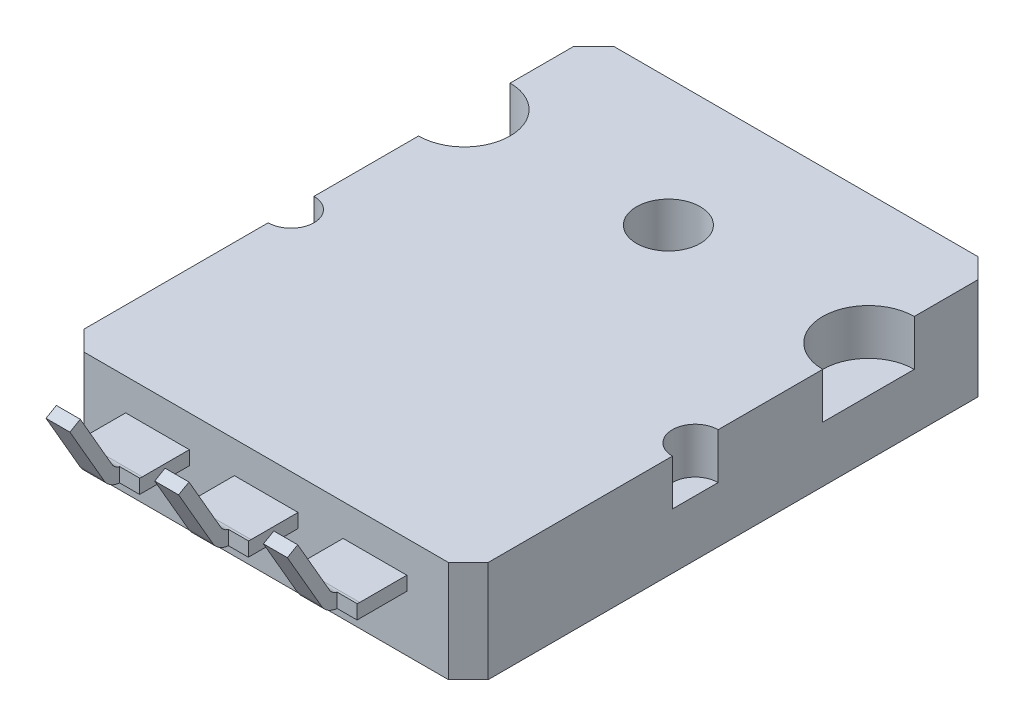
SolidWorks part; units mm, degrees
ref_plane "Спереди" through (0, 0, 0) normal (0, 0, 1) x (1, 0, 0)
ref_plane "Сверху" through (0, 0, 0) normal (0, 1, 0) x (1, 0, 0)
ref_plane "Справа" through (0, 0, 0) normal (1, 0, 0) x (0, 0, -1)
ref_plane "Плоскость1" through (0, 2.3, 0) normal (0, 1, 0) x (1, 0, 0)
sketch "Эскиз1" plane through (0, 2.3, 0) normal (0, 1, 0) x (1, 0, 0)
  line L0 (-10.15, -13.3) -> (10.15, -13.3)
  line L1 (10.15, -13.3) -> (10.15, 13.3)
  line L2 (10.15, 13.3) -> (-10.15, 13.3)
  line L3 (-10.15, 13.3) -> (-10.15, -13.3)
extrude "Бобышка-Вытянуть1" add sketch "Эскиз1" against normal blind 5.1
sketch "Эскиз2" plane through (0, 0, 13.3) normal (0, 0, 1) x (1, 0, 0)
  line L0 (3.861, 0) -> (3.861, 0.7)
  line L1 (3.861, 0.7) -> (7.061, 0.7)
  line L2 (7.061, 0.7) -> (7.061, 0)
  line L3 (7.061, 0) -> (3.861, 0)
extrude "Бобышка-Вытянуть2" add sketch "Эскиз2" along normal blind 3
sketch "Эскиз3" plane through (0, 0, 0) normal (0, -1, 0) x (1, 0, 0)
  line L0 (3.861, 15.8) -> (4.861, 15.8)
  line L1 (4.861, 15.8) -> (4.861, 18.3)
  line L2 (4.861, 18.3) -> (3.861, 18.3)
  line L3 (3.861, 18.3) -> (3.861, 15.8)
extrude "Вырез-Вытянуть1" cut sketch "Эскиз3" against normal through all
sketch "Эскиз4" plane through (0, 0, 0) normal (0, -1, 0) x (1, 0, 0)
  line L0 (6.061, 18.3) -> (6.061, 15.8)
  line L1 (6.061, 15.8) -> (7.061, 15.8)
  line L2 (7.061, 15.8) -> (7.061, 18.3)
  line L3 (7.061, 18.3) -> (6.061, 18.3)
extrude "Вырез-Вытянуть2" cut sketch "Эскиз4" against normal through all
sketch "Эскиз6" plane through (0, 0, 13.3) normal (0, 0, 1) x (1, 0, 0)
  line L0 (-1.6, 0) -> (-1.6, 0.7)
  line L1 (-1.6, 0.7) -> (1.6, 0.7)
  line L2 (1.6, 0.7) -> (1.6, 0)
  line L3 (1.6, 0) -> (-1.6, 0)
extrude "Бобышка-Вытянуть4" add sketch "Эскиз6" along normal blind 3
sketch "Эскиз7" plane through (0, 0, 0) normal (0, -1, 0) x (1, 0, 0)
  line L0 (-0.6, 15.8) -> (-0.6, 18.3)
  line L1 (-0.6, 18.3) -> (-1.6, 18.3)
  line L2 (-1.6, 18.3) -> (-1.6, 15.8)
  line L3 (-1.6, 15.8) -> (-0.6, 15.8)
extrude "Вырез-Вытянуть3" cut sketch "Эскиз7" against normal through all
sketch "Эскиз8" plane through (0, 0, 0) normal (0, -1, 0) x (1, 0, 0)
  line L0 (1.6, 18.3) -> (0.6, 18.3)
  line L1 (0.6, 18.3) -> (0.6, 15.8)
  line L2 (0.6, 15.8) -> (1.6, 15.8)
  line L3 (1.6, 15.8) -> (1.6, 18.3)
extrude "Вырез-Вытянуть4" cut sketch "Эскиз8" against normal through all
sketch "Эскиз10" plane through (0, 0, 13.3) normal (0, 0, 1) x (1, 0, 0)
  line L0 (-7.061, 0) -> (-7.061, 0.7)
  line L1 (-7.061, 0.7) -> (-3.861, 0.7)
  line L2 (-3.861, 0.7) -> (-3.861, 0)
  line L3 (-3.861, 0) -> (-7.061, 0)
extrude "Бобышка-Вытянуть6" add sketch "Эскиз10" along normal blind 3
sketch "Эскиз11" plane through (0, 0, 0) normal (0, -1, 0) x (1, 0, 0)
  line L0 (-6.061, 15.8) -> (-6.061, 18.3)
  line L1 (-6.061, 18.3) -> (-7.061, 18.3)
  line L2 (-7.061, 18.3) -> (-7.061, 15.8)
  line L3 (-7.061, 15.8) -> (-6.061, 15.8)
extrude "Вырез-Вытянуть5" cut sketch "Эскиз11" against normal through all
sketch "Эскиз12" plane through (0, 0, 0) normal (0, -1, 0) x (1, 0, 0)
  line L0 (-3.861, 18.3) -> (-4.861, 18.3)
  line L1 (-4.861, 18.3) -> (-4.861, 15.8)
  line L2 (-4.861, 15.8) -> (-3.861, 15.8)
  line L3 (-3.861, 15.8) -> (-3.861, 18.3)
extrude "Вырез-Вытянуть6" cut sketch "Эскиз12" against normal through all
hole_wizard "Диаметр отверстия Ø3.2 (3.2)1" positions "Эскиз15" profile "Эскиз14" hole size "Ø3.2" standard "Ansi Metric"
sketch "Эскиз15" plane through (0, 2.3, 0) normal (0, 1, 0) x (1, 0, 0)
  point P0 (0, 6.9)
sketch "Эскиз14" plane through (0, 2.3, -6.9) normal (1, 0, 0) x (0, 0, 1)
  line L0 (0, 0) -> (0, 5.1)
  line L1 (0, 5.1) -> (1.6, 5.1)
  line L2 (1.6, 5.1) -> (1.6, 0)
  line L5 (1.6, 0) -> (0, 0)
  line L11 (0, -6.35) -> (0, 107.95) construction
  dimension "Диаметр сквозного отверстия" = 3.2
  dimension "Глубина сквозного отверстия" = 5.1
hole_wizard "Диаметр отверстия Ø2.3 (2.3)1" positions "Эскиз17" profile "Эскиз16" hole size "Ø2.3" standard "Ansi Metric"
sketch "Эскиз17" plane through (0, 2.3, 0) normal (0, 1, 0) x (1, 0, 0)
  point P0 (10.15, -1.9)
  point P1 (-10.15, -1.9)
sketch "Эскиз16" plane through (10.15, 2.3, 1.9) normal (1, 0, 0) x (0, 0, 1)
  line L0 (0, 0) -> (0, 2.3)
  line L1 (0, 2.3) -> (1.15, 2.3)
  line L2 (1.15, 2.3) -> (1.15, 0)
  line L5 (1.15, 0) -> (0, 0)
  line L10 (0, 2.3) -> (-1.15, 2.3) construction
  line L11 (0, -6.35) -> (0, 107.95) construction
  dimension "Диаметр отверстия" = 2.3
  dimension "Глубина отверстия" = 2.3
  dimension "Угол заточки сверла" = 180
hole_wizard "Диаметр отверстия Ø4.6 (4.6)1" positions "Эскиз19" profile "Эскиз18" hole size "Ø4.6" standard "Ansi Metric"
sketch "Эскиз19" plane through (0, 2.3, 0) normal (0, 1, 0) x (1, 0, 0)
  point P0 (10.15, 6.8)
  point P1 (-10.15, 6.8)
sketch "Эскиз18" plane through (10.15, 2.3, -6.8) normal (1, 0, 0) x (0, 0, 1)
  line L0 (0, 0) -> (0, 2.3)
  line L1 (0, 2.3) -> (2.3, 2.3)
  line L2 (2.3, 2.3) -> (2.3, 0)
  line L5 (2.3, 0) -> (0, 0)
  line L10 (0, 2.3) -> (-2.3, 2.3) construction
  line L11 (0, -6.35) -> (0, 107.95) construction
  dimension "Диаметр отверстия" = 4.6
  dimension "Глубина отверстия" = 2.3
  dimension "Угол заточки сверла" = 180
chamfer "Фаска1" distance 1 angle 45 4 edges at (10.15, -0.25, 13.3) (-10.15, -0.25, 13.3) (10.15, -0.25, -13.3) (-10.15, -0.25, -13.3)
sketch "Эскиз20" plane through (0, -2.8, 0) normal (0, -1, 0) x (1, 0, 0)
  line L0 (9.15, -11.8858) -> (9.15, 11.8858)
  line L1 (9.15, 11.8858) -> (8.7358, 12.3)
  line L2 (8.7358, 12.3) -> (-8.7358, 12.3)
  line L3 (-8.7358, 12.3) -> (-9.15, 11.8858)
  line L4 (-9.15, 11.8858) -> (-9.15, -11.8858)
  line L5 (-9.15, -11.8858) -> (-8.7358, -12.3)
  line L6 (-8.7358, -12.3) -> (8.7358, -12.3)
  line L7 (8.7358, -12.3) -> (9.15, -11.8858)
  line L8 (10.15, -12.3) -> (10.15, 12.3)
  line L9 (10.15, 12.3) -> (9.15, 13.3)
  line L10 (9.15, 13.3) -> (-9.15, 13.3)
  line L11 (-9.15, 13.3) -> (-10.15, 12.3)
  line L12 (-10.15, 12.3) -> (-10.15, -12.3)
  line L13 (-10.15, -12.3) -> (-9.15, -13.3)
  line L14 (-9.15, -13.3) -> (9.15, -13.3)
  line L15 (9.15, -13.3) -> (10.15, -12.3)
  line L16 (10.15, -12.3) -> (10.15, 12.3)
  line L17 (10.15, 12.3) -> (9.15, 13.3)
  line L18 (9.15, 13.3) -> (-9.15, 13.3)
  line L19 (-9.15, 13.3) -> (-10.15, 12.3)
  line L20 (-10.15, 12.3) -> (-10.15, -12.3)
  line L21 (-10.15, -12.3) -> (-9.15, -13.3)
  line L22 (-9.15, -13.3) -> (9.15, -13.3)
  line L23 (9.15, -13.3) -> (10.15, -12.3)
  circle A0 centre (0, -6.9) radius 1.6 construction
  circle M9 centre (0, -6.9) radius 1.6
  dimension "D1" = 0
  dimension "D2" = 1
extrude "Вырез-Вытянуть7" cut sketch "Эскиз20" against normal blind 1.5 contours L6 L7 L0 L1 L2 L3 L4 L5 M9 region at (0, -2.8, 0.1256)
ref_plane "Плоскость2" through (0, -7.0581, 12.225) normal (0, -0.5, 0.866) x (1, 0, 0)
ref_plane "Плоскость3" through (0, 7.0581, 4.075) normal (0, -0.866, -0.5) x (1, 0, 0)
sketch "Эскиз21" plane through (0, 7.0581, 4.075) normal (0, -0.866, -0.5) x (1, 0, 0)
  line L0 (-6.061, 13.6832) -> (-6.061, 14.1162) construction
  line L1 (-6.061, 14.1162) -> (-4.861, 14.1162)
  line L2 (-6.061, 14.1162) -> (-6.061, 13.5162)
  line L3 (-6.061, 13.5162) -> (-4.861, 13.5162)
  line L4 (-4.861, 14.1162) -> (-4.861, 13.5162)
  line L5 (-6.061, 14.1162) -> (-4.861, 13.5162) construction
  line L6 (-6.061, 13.5162) -> (-4.861, 14.1162) construction
  line L9 (-0.6, 13.5162) -> (0.6, 13.5162)
  line L10 (0.6, 14.1162) -> (0.6, 13.5162)
  line L11 (-0.6, 14.1162) -> (0.6, 14.1162)
  line L12 (-0.6, 14.1162) -> (-0.6, 13.5162)
  line L13 (4.861, 13.5162) -> (6.061, 13.5162)
  line L14 (6.061, 14.1162) -> (6.061, 13.5162)
  line L15 (4.861, 14.1162) -> (6.061, 14.1162)
  line L16 (4.861, 14.1162) -> (4.861, 13.5162)
  line L17 (-3.861, 11.5181) -> (-3.861, 13.6832)
  line L18 (-3.861, 13.6832) -> (-4.861, 13.6832)
  line L19 (-4.861, 13.6832) -> (-4.861, 14.1162)
  line L20 (-4.861, 14.1162) -> (-6.061, 14.1162)
  line L21 (-6.061, 14.1162) -> (-6.061, 13.6832)
  line L22 (-6.061, 13.6832) -> (-7.061, 13.6832)
  line L23 (-7.061, 13.6832) -> (-7.061, 11.5181)
  line L24 (-7.061, 11.5181) -> (-3.861, 11.5181)
  line L25 (-3.861, 11.5181) -> (-3.861, 13.6832)
  line L26 (-3.861, 13.6832) -> (-4.861, 13.6832)
  line L27 (-4.861, 13.6832) -> (-4.861, 14.1162)
  line L28 (-4.861, 14.1162) -> (-6.061, 14.1162)
  line L29 (-6.061, 14.1162) -> (-6.061, 13.6832)
  line L30 (-6.061, 13.6832) -> (-7.061, 13.6832)
  line L31 (-7.061, 13.6832) -> (-7.061, 11.5181)
  line L32 (-7.061, 11.5181) -> (-3.861, 11.5181)
  point P4 (-5.461, 13.8162)
  point P9 (4.861, 14.1162)
  point P10 (-0.6, 14.1162)
  dimension "D2" = 0.6
  dimension "D1" = 0
  dimension "D3" = 3
extrude "Бобышка-Вытянуть10" add sketch "Эскиз21" against normal blind 4 contours L4 L1 L2 L3 | L11 L12 L9 L10 | L15 L16 L13 L14 region at (-5.461, 0.15, 16.0402) region at (0, 0.15, 16.0402) region at (5.461, 0.15, 16.0402)
fillet "Скругление1" radius 1 3 edges at (5.461, 0, 16.3) (0, 0, 16.3) (-5.461, 0, 16.3)
fillet "Скругление2" radius 0.6 3 edges at (-5.461, 0.7, 16.0113) (0, 0.7, 16.0113) (5.461, 0.7, 16.0113)
